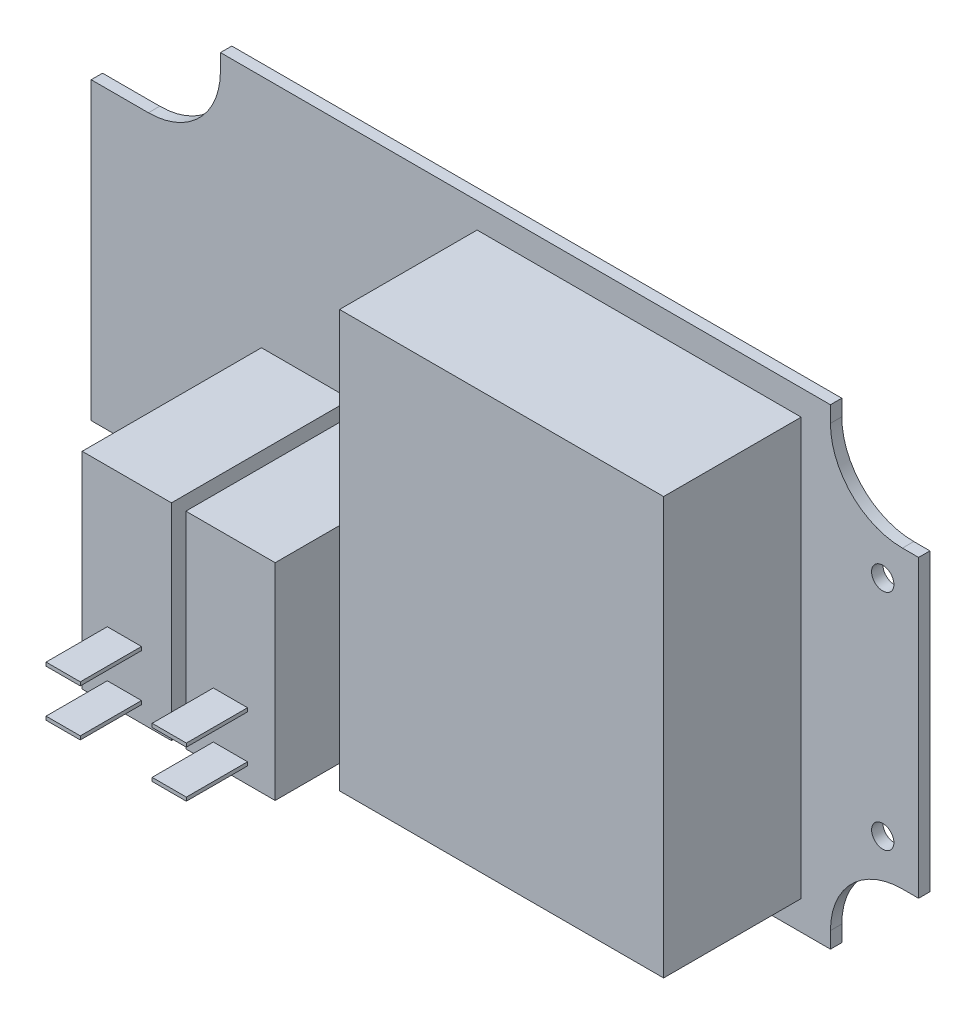
SolidWorks part; units mm, degrees
ref_plane "Front Plane" through (0, 0, 0) normal (0, 0, 1) x (1, 0, 0)
ref_plane "Top Plane" through (0, 0, 0) normal (0, 1, 0) x (1, 0, 0)
ref_plane "Right Plane" through (0, 0, 0) normal (1, 0, 0) x (0, 0, -1)
sketch "Sketch1" plane through (0, 0, 0) normal (0, 0, 1) x (1, 0, 0)
  line L0 (-42.3541, 30.2967) -> (-52.3541, 30.2967) construction
  line L1 (42.3541, -30.7033) -> (42.3541, -32.9433)
  line L2 (-52.3541, -20.7033) -> (-60.3013, -20.7033)
  line L4 (52.3541, -20.7033) -> (54.5933, -20.7033)
  line L5 (-52.3541, 30.2967) -> (-52.3541, 20.2967) construction
  line L6 (-52.3541, -20.7033) -> (-52.3541, -30.7033) construction
  line L7 (-52.3541, -30.7033) -> (-42.3541, -30.7033) construction
  line L8 (42.3541, -30.7033) -> (52.3541, -30.7033) construction
  line L9 (52.3541, -30.7033) -> (52.3541, -20.7033) construction
  line L10 (52.3541, 20.2967) -> (52.3541, 30.2967) construction
  line L11 (52.3541, 30.2967) -> (42.3541, 30.2967) construction
  line L12 (54.5933, -20.7033) -> (54.5933, 20.2967)
  line L13 (-60.3013, -20.7033) -> (-60.3013, 20.2967)
  line L14 (-60.3013, 20.2967) -> (-52.3541, 20.2967)
  line L15 (54.5933, 20.2967) -> (52.3541, 20.2967)
  line L16 (42.3541, -32.9433) -> (-42.3541, -32.9433)
  line L17 (-42.3541, -32.9433) -> (-42.3541, -30.7033)
  line L21 (0, -32.9433) -> (0, 0) construction
  line L24 (42.3541, 30.2967) -> (42.3541, 32.5367)
  line L25 (42.3541, 32.5367) -> (-42.3541, 32.5367)
  line L26 (-42.3541, 32.5367) -> (-42.3541, 30.2967)
  arc A0 (-42.3541, 30.2967) -> (-52.3541, 20.2967) centre (-52.3541, 30.2967) cw
  circle A1 centre (49.6183, -15.7283) radius 1.55
  arc A2 (-52.3541, -20.7033) -> (-42.3541, -30.7033) centre (-52.3541, -30.7033) cw
  circle A3 centre (49.6183, 15.3217) radius 1.55
  arc A4 (42.3541, 30.2967) -> (52.3541, 20.2967) centre (52.3541, 30.2967) ccw
  arc A5 (52.3541, -20.7033) -> (42.3541, -30.7033) centre (52.3541, -30.7033) ccw
  dimension "D1" = 41
  dimension "D2" = 3.1
  dimension "D3" = 10
  dimension "D4" = 4.975
  dimension "D5" = 84.7082
  dimension "D6" = 2.24
  dimension "D7" = 7.9472
  dimension "D8" = 2.2392
  dimension "D9" = 4.975
  dimension "D10" = 4.975
extrude "Boss-Extrude1" add sketch "Sketch1" along normal blind 1.5748
sketch "Sketch2" plane through (0, 0, 1.5748) normal (0, 0, 1) x (1, 0, 0)
  line L1 (-36.6572, -0.1162) -> (-24.2572, -0.1162)
  line L2 (-36.6572, -0.1162) -> (-36.6572, -28.7162)
  line L3 (-36.6572, -28.7162) -> (-24.2572, -28.7162)
  line L4 (-24.2572, -0.1162) -> (-24.2572, -28.7162)
  line L5 (-22.2572, -0.1162) -> (-9.8572, -0.1162)
  line L6 (-22.2572, -0.1162) -> (-22.2572, -28.7162)
  line L7 (-22.2572, -28.7162) -> (-9.8572, -28.7162)
  line L8 (-9.8572, -0.1162) -> (-9.8572, -28.7162)
  dimension "D1" = 2
  dimension "D2" = 28.6
  dimension "D3" = 12.4
extrude "Boss-Extrude2" add sketch "Sketch2" along normal blind 24.9
sketch "Sketch3" plane through (0, 0, 26.4748) normal (0, 0, 1) x (1, 0, 0)
  line L1 (-13.6892, -26.4707) -> (-18.4392, -26.4707)
  line L2 (-13.6892, -26.4707) -> (-13.6892, -25.9707)
  line L3 (-13.6892, -25.9707) -> (-18.4392, -25.9707)
  line L4 (-18.4392, -26.4707) -> (-18.4392, -25.9707)
  line L5 (-13.6892, -19.9707) -> (-18.4392, -19.9707)
  line L6 (-13.6892, -19.9707) -> (-13.6892, -19.4707)
  line L7 (-13.6892, -19.4707) -> (-18.4392, -19.4707)
  line L8 (-18.4392, -19.9707) -> (-18.4392, -19.4707)
  line L9 (-28.4177, -26.4707) -> (-33.1677, -26.4707)
  line L10 (-28.4177, -26.4707) -> (-28.4177, -25.9707)
  line L11 (-28.4177, -25.9707) -> (-33.1677, -25.9707)
  line L12 (-33.1677, -26.4707) -> (-33.1677, -25.9707)
  line L13 (-28.4177, -19.9707) -> (-33.1677, -19.9707)
  line L14 (-28.4177, -19.9707) -> (-28.4177, -19.4707)
  line L15 (-28.4177, -19.4707) -> (-33.1677, -19.4707)
  line L16 (-33.1677, -19.9707) -> (-33.1677, -19.4707)
  dimension "D1" = 0.5
  dimension "D2" = 4.75
  dimension "D3" = 6
extrude "Boss-Extrude3" add sketch "Sketch3" along normal blind 8.5
sketch "Sketch4" plane through (0, 0, 1.5748) normal (0, 0, 1) x (1, 0, 0)
  line L1 (38.2866, -28.8884) -> (-6.7134, -28.8884)
  line L2 (38.2866, -28.8884) -> (38.2866, 29.0116)
  line L3 (38.2866, 29.0116) -> (-6.7134, 29.0116)
  line L4 (-6.7134, -28.8884) -> (-6.7134, 29.0116)
  dimension "D1" = 57.9
  dimension "D2" = 45
extrude "Boss-Extrude4" add sketch "Sketch4" along normal blind 19.1
